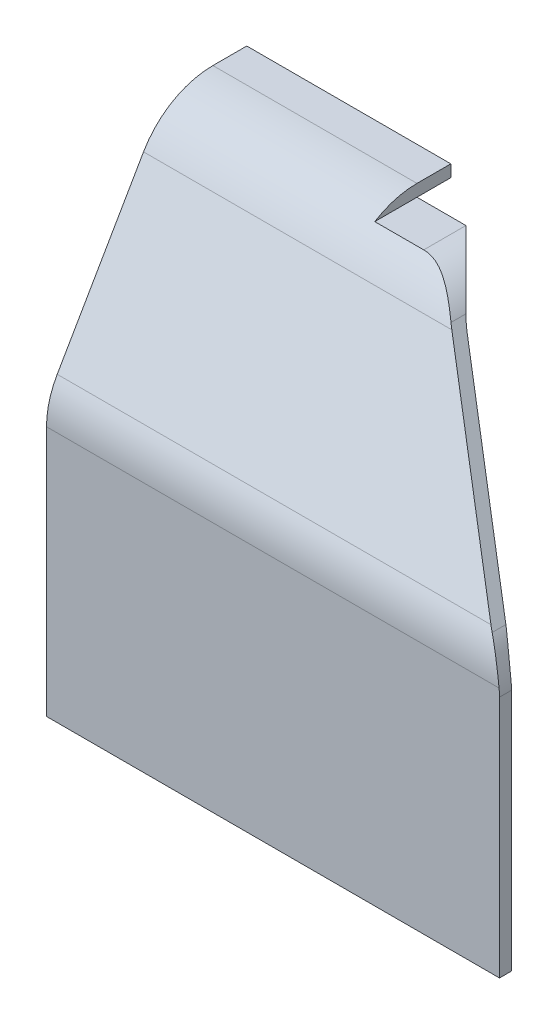
SolidWorks part; units mm, degrees
ref_plane "Alzado" through (0, 0, 0) normal (0, 0, 1) x (1, 0, 0)
ref_plane "Planta" through (0, 0, 0) normal (0, 1, 0) x (1, 0, 0)
ref_plane "Vista lateral" through (0, 0, 0) normal (1, 0, 0) x (0, 0, -1)
sketch "Croquis1" plane through (0, 0, 0) normal (1, 0, 0) x (0, 0, -1)
  line L0 (0, 0) -> (0, 67.1962)
  line L1 (0, 67.1962) -> (28.7321, 116.9615)
  line L2 (28.7321, 116.9615) -> (47, 116.9615)
  line L3 (47, 116.9615) -> (47, 119.9615)
  line L4 (47, 119.9615) -> (27, 119.9615)
  line L5 (27, 119.9615) -> (-3, 68)
  line L6 (-3, 68) -> (-3, 0)
  line L7 (-3, 0) -> (0, 0)
  line L8 (0, 67.1962) -> (29.2398, 67.1962) construction
  dimension "D1" = 3
  dimension "D2" = 3
  dimension "D3" = 3
  dimension "D4" = 68
  dimension "D5" = 60
  dimension "D6" = 20
  dimension "D7" = 60
extrude "Saliente-Extruir1" add sketch "Croquis1" along normal mid plane 116.1
fillet "Redondeo1" radius 20 1 edges at (0, 68, 3)
fillet "Redondeo2" radius 20 1 edges at (0, 119.9615, -27)
fillet "Redondeo3" radius 17 1 edges at (0, 116.9615, -28.7321)
fillet "Redondeo4" radius 17 1 edges at (0, 67.1962, 0)
sketch "Croquis3" plane through (0, 0, 0) normal (0, 0, -1) x (-1, 0, 0)
  line L8 (-55.05, 0) -> (-55.05, 60.7206)
  line L13 (-51.0728, 71.648) -> (-18.1457, 110.8889)
  line L14 (-5.123, 116.9615) -> (7.1009, 116.9615)
  line L15 (7.1009, 116.9615) -> (7.1009, 119.9615)
  line L16 (7.1009, 119.9615) -> (-3.573, 119.9615)
  line L18 (-58.05, 60.7206) -> (-58.05, 0)
  line L19 (-58.05, 0) -> (-55.05, 0)
  line L20 (-55.05, 66.9081) -> (-24.2602, 66.9081) construction
  line L21 (-58.05, 0) -> (-58.05, 62.641) construction
  line L22 (-58.05, 0) -> (58.05, 0) construction
  line L23 (-3.573, 119.9615) -> (-58.05, 119.9615)
  line L24 (-58.05, 119.9615) -> (-58.05, 60.7206)
  arc A2 (-55.05, 60.7206) -> (-51.0728, 71.648) centre (-38.05, 60.7206) cw
  arc A3 (-18.1457, 110.8889) -> (-5.123, 116.9615) centre (-5.123, 99.9615) cw
  point P19 (-56.5004, 67.9823)
  dimension "D9" = 17
  dimension "D1" = 3
  dimension "D3" = 3
  dimension "D4" = 68
  dimension "D6" = 119.9615
  dimension "D7" = 50
extrude "Cortar-Extruir1" cut sketch "Croquis3" along normal mid plane 100
